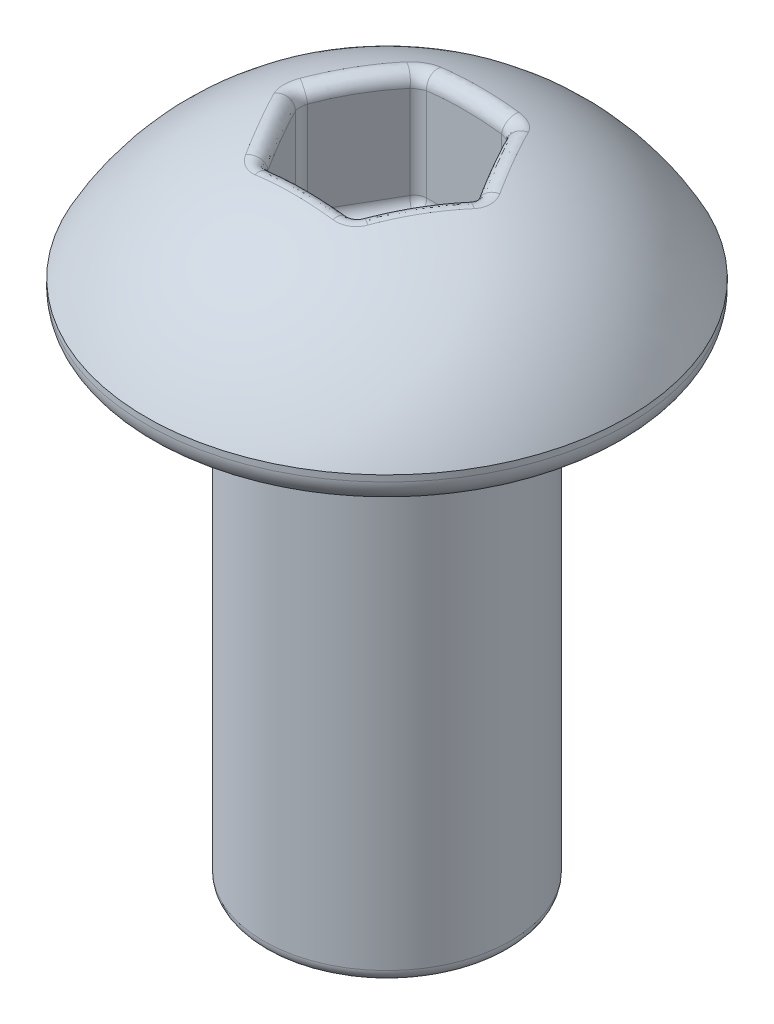
SolidWorks part; units mm, degrees
material "铸造碳钢"
ref_plane "Front" through (0, 0, 0) normal (0, 0, 1) x (1, 0, 0)
ref_plane "Top" through (0, 0, 0) normal (0, 1, 0) x (1, 0, 0)
ref_plane "Right" through (0, 0, 0) normal (1, 0, 0) x (0, 0, -1)
sketch "草图1" plane through (0, 0, 0) normal (0, 1, 0) x (1, 0, 0)
  circle A0 centre (0, 0) radius 2
  dimension "螺丝直径" = 4
extrude "凸台-拉伸1" add sketch "草图1" against normal blind 8
sketch "草图2" plane through (0, 0, 0) normal (0, 0, 1) x (1, 0, 0)
  line L0 (0, -1000) -> (0, 49000) construction
  line L1 (-1000, 0) -> (49000, 0) construction
  line L2 (-3.9, 0) -> (3.9, 0) construction
  line L3 (-999.5875, 2.5) -> (49000.4125, 2.5) construction
  line L4 (-3.9, -1000) -> (-3.9, 49000) construction
  line L5 (3.9, -1000) -> (3.9, 49000) construction
  line L6 (-3.9, 0.5) -> (3.9, 0.5) construction
  line L7 (1.25, 2.5) -> (-1.25, 2.5)
  line L8 (-3.9, 0.5) -> (-3.9, 0.4)
  line L9 (-3.5, 0) -> (3.5, 0)
  line L10 (3.9, 0.4) -> (3.9, 0.5)
  line L11 (0, 2.5) -> (0, 0)
  arc A0 (3.5, 0) -> (3.9, 0.4) centre (3.5, 0.4) ccw
  arc A1 (-3.9, 0.4) -> (-3.5, 0) centre (-3.5, 0.4) ccw
  arc A2 (-3.9, 0.5) -> (-1.25, 2.5) centre (-0.3827, -1.4048) cw
  arc A3 (3.9, 0.5) -> (1.25, 2.5) centre (0.3827, -1.4048) ccw
  point P18 (0, 2.5)
  dimension "D2" = 0.4
  dimension "D3" = 4
  dimension "D1" = 0.5
  dimension "螺丝头半径" = 3.9
  dimension "螺丝头厚度" = 2.5
  dimension "六角直径" = 2.5
revolve "旋转1" add sketch "草图2" angle 360 about L0 region at (-1.6557, 1.0961, 0)
sketch "草图3" plane through (0, 2.5, 0) normal (0, 1, 0) x (1, 0, 0)
  line L1 (1.4434, 0) -> (0.7217, 1.25)
  line L2 (0.7217, 1.25) -> (-0.7217, 1.25)
  line L3 (-0.7217, 1.25) -> (-1.4434, 0)
  line L4 (-1.4434, 0) -> (-0.7217, -1.25)
  line L5 (-0.7217, -1.25) -> (0.7217, -1.25)
  line L6 (0.7217, -1.25) -> (1.4434, 0)
  circle A0 centre (0, 0) radius 1.25 construction
  dimension "六角直径2" = 2.5
extrude "切除-拉伸1" cut sketch "草图3" against normal blind 2 and the other way through all contours L2 L3 L4 L5 L6 L1
fillet "圆角1" radius 0.2 19 edges at (1.0825, 0.5, -0.625) (-1.0825, 0.5, -0.625) (-1.4434, 1.476, 0) (-1.0825, 0.5, 0.625) (-0.7217, 1.476, 1.25) (0, 0.5, 1.25) (0.7217, 1.476, 1.25) (1.0825, 0.5, 0.625) (1.4434, 1.476, 0) (0.7217, 1.476, -1.25) (0, 0.5, -1.25) (-0.7217, 1.476, -1.25) (0, -8, 2)
other "冻结***"
equation "\"2。8\"=3"
